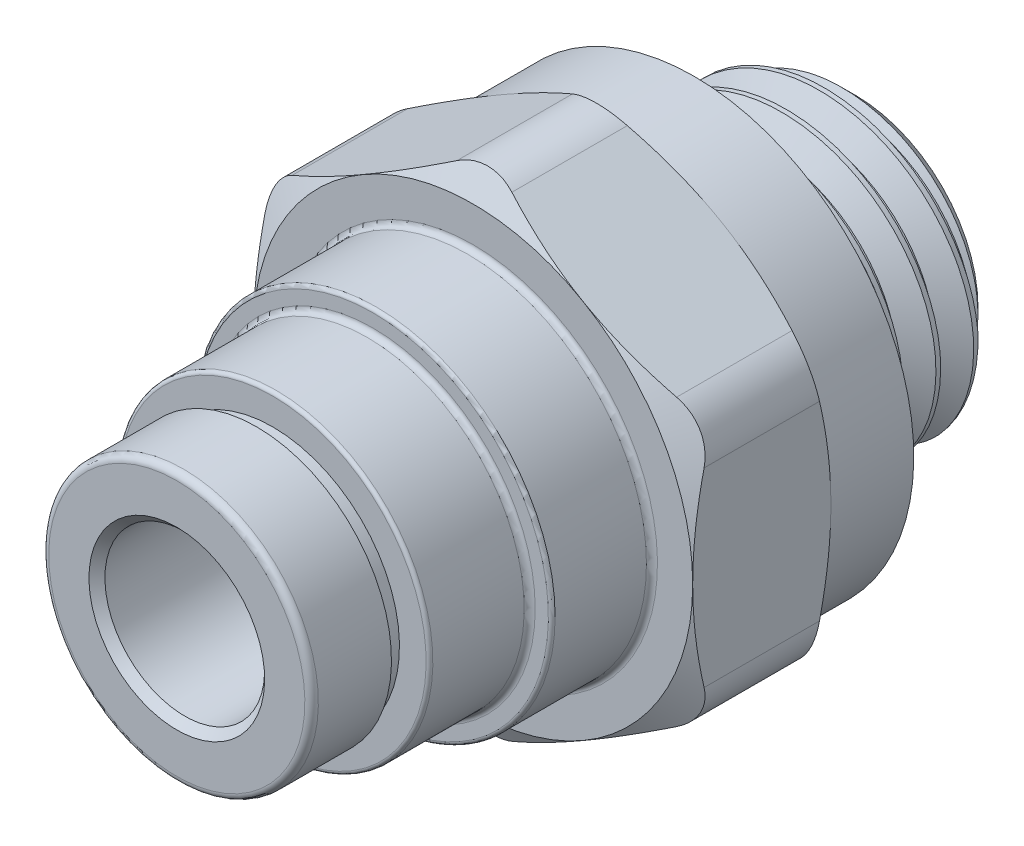
SolidWorks part; units mm, degrees
ref_plane "Front Plane" through (0, 0, 0) normal (0, 0, 1) x (1, 0, 0)
ref_plane "Top Plane" through (0, 0, 0) normal (0, 1, 0) x (1, 0, 0)
ref_plane "Right Plane" through (0, 0, 0) normal (1, 0, 0) x (0, 0, -1)
sketch "Sketch1" plane through (0, 0, 0) normal (1, 0, 0) x (0, 0, -1)
  line L0 (13.4937, 0) -> (-13.4937, 0) construction
  line L1 (-13.4937, -7.112) -> (-13.4938, 7.112) construction
  line L2 (-1.7158, -8.7313) -> (-1.7158, 8.7312) construction
  line L3 (1.4465, -2.3876) -> (1.4465, 2.3876) construction
  line L4 (13.4938, -6) -> (13.4938, 6) construction
  line L6 (13.4938, 6) -> (14.9938, 6) construction
  point P0 (-13.4937, -3.175)
  point P3 (7.0726, 0)
  point P4 (0, 0)
  point P8 (-13.4937, 0)
  point P9 (-13.4937, 3.175)
  point P10 (-13.4937, -5.3594)
  point P11 (-13.4937, 5.3594)
  point P16 (-1.7158, 0)
  point P19 (13.4937, 0)
  point P22 (1.4465, 0)
  dimension "Length" = 26.9875
  dimension "OD2" = 14.224
  dimension "Tube OD" = 6.35
  dimension "OD1" = 10.7188
  dimension "Hex Distance" = 11.778
  dimension "Hex Size" = 17.4625
  dimension "Flow" = 4.7752
  dimension "Insertion" = 14.9403
  dimension "Thread OD" = 12
  dimension "Pitch" = 1.5
  dimension "Hex Length" = 8.7884
sketch "Sketch2" plane through (0, 0, 0) normal (1, 0, 0) x (0, 0, -1)
  line L0 (-13.4938, 3.4925) -> (-13.4938, 5.0914)
  line L1 (-13.2258, 5.3594) -> (-10.3187, 5.3594)
  line L2 (-10.3187, 5.3594) -> (-10.3187, 5.0419)
  line L3 (-10.3187, 5.0419) -> (-9.6837, 5.0419)
  line L4 (-9.6837, 5.0419) -> (-9.6837, 6.1017)
  line L5 (-5.5658, 7.112) -> (-1.9348, 7.112)
  line L6 (-1.7158, -8.7313) -> (-1.7158, 8.7312) construction
  line L7 (-1.7158, 7.3311) -> (-1.7158, 8.7312)
  line L8 (-1.7158, 8.7312) -> (7.0726, 8.7312)
  line L11 (13.4938, 6) -> (13.4938, 2.3876)
  line L12 (13.4938, 2.3876) -> (1.4465, 2.3876)
  line L13 (1.4465, 2.3876) -> (1.4465, 3.175)
  line L14 (1.4465, 3.175) -> (-13.1762, 3.175)
  line L16 (-13.4938, 3.4925) -> (-13.1762, 3.175)
  line L17 (-9.5498, 6.2357) -> (-5.9188, 6.2357)
  line L18 (-5.6998, 6.4548) -> (-5.6998, 6.978)
  line L22 (7.0726, 8.7312) -> (7.0726, 6.7143)
  line L23 (6.7551, 6.1644) -> (7.3901, 6.1644) construction
  line L24 (13.4938, 6) -> (7.4975, 6)
  line L25 (6.7551, 6.1644) -> (7.0726, 6.7143) construction
  line L26 (6.7551, 6.1644) -> (7.3685, 6) construction
  line L27 (7.4975, 6) -> (7.1975, 5.7087)
  arc A0 (-13.2258, 5.3594) -> (-13.4938, 5.0914) centre (-13.2258, 5.0914) ccw
  arc A1 (-1.7158, 7.3311) -> (-1.9348, 7.112) centre (-1.9348, 7.3311) cw
  arc A2 (-5.6998, 6.4548) -> (-5.9188, 6.2357) centre (-5.9188, 6.4548) cw
  circle A4 centre (6.7551, 6.1644) radius 0.635 construction
  arc A5 (7.0726, 6.7143) -> (7.1975, 5.7087) centre (6.7551, 6.1644) cw
  arc A6 (-5.5658, 7.112) -> (-5.6998, 6.978) centre (-5.5658, 6.978) ccw
  arc A7 (-9.5498, 6.2357) -> (-9.6837, 6.1017) centre (-9.5498, 6.1017) ccw
  point P28 (-13.4937, 5.3594)
  point P32 (-1.7158, 7.112)
  point P35 (-5.6998, 6.2357)
  point P40 (-5.6998, 7.112)
  dimension "D6" = 0.268
  dimension "D5" = 0.2191
  dimension "D13" = 0.134
  dimension "D1" = 3.175
  dimension "D2" = 0.635
  dimension "D3" = 0.3175
  dimension "D7" = 0.3175
  dimension "D8" = 45
  dimension "D4" = 0.8763
  dimension "D9" = 60
  dimension "D10" = 0.3175
  dimension "D11" = 15
  dimension "D12" = 0.3
revolve "Revolve1" add sketch "Sketch2" angle 360 about L0
sketch "Sketch3" plane through (0, 0, 1.7158) normal (0, 0, 1) x (1, 0, 0)
  line L0 (0, -7.112) -> (0, 7.112) construction
  line L1 (0, 10.082) -> (-8.7313, 5.041)
  line L2 (-8.7313, 5.041) -> (-8.7312, -5.041)
  line L3 (-8.7312, -5.041) -> (0, -10.082)
  line L4 (0, -10.082) -> (8.7312, -5.041)
  line L5 (8.7312, -5.041) -> (8.7312, 5.041)
  line L6 (8.7312, 5.041) -> (0, 10.082)
  circle A0 centre (0, 0) radius 8.7312 construction
  circle A1 centre (0, 0) radius 8.7312 construction
  circle A2 centre (0, 0) radius 3.175
extrude "Boss-Extrude1" add sketch "Sketch3" against normal blind 5.4927
sketch "Sketch4" plane through (0, 0, 1.7158) normal (0, 0, 1) x (1, 0, 0)
  circle A0 centre (0, 0) radius 8.7312 construction
  circle A1 centre (0, 0) radius 8.7312
extrude "Cut-Extrude1" cut sketch "Sketch4" against normal through all draft 60 flip side to cut
ref_plane "Plane1" through (0, 0, -1.0306) normal (0, 0, 1) x (1, 0, 0)
mirror "Mirror1" about plane through (0, 0, -1.0306) normal (0, 0, 1) of "Cut-Extrude1"
sketch "Sketch9" plane through (0, 0, 0) normal (1, 0, 0) x (0, 0, -1)
  line L0 (1.4465, -3.175) -> (-13.1762, -3.175)
  line L1 (-13.1763, 3.175) -> (1.4465, 3.175)
  line L2 (-13.1763, 3.175) -> (1.4465, 3.175)
  line L3 (1.4465, -3.175) -> (-13.1762, -3.175)
  line L4 (-13.4938, 3.4925) -> (-13.1763, 3.175)
  line L5 (-13.1762, -3.175) -> (-13.4938, -3.4925)
  line L6 (-13.1762, -3.175) -> (-13.4938, -3.4925)
  line L7 (-13.4938, 3.4925) -> (-13.1763, 3.175)
  line L8 (13.4938, -2.3876) -> (1.4465, -2.3876)
  line L9 (1.4465, 2.3876) -> (13.4938, 2.3876)
  line L10 (1.4465, 2.3876) -> (13.4938, 2.3876)
  line L11 (13.4938, -2.3876) -> (1.4465, -2.3876)
  line L12 (1.4465, 3.175) -> (1.4465, 2.3876)
  line L13 (1.4465, -2.3876) -> (1.4465, -3.175)
  line L14 (13.4937, 0) -> (13.4938, -6) construction
  line L16 (13.4938, -6) -> (9.7438, -6) construction
  dimension "D1" = 3.75
fillet "Fillet1" radius 2.1828 6 edges at (8.7312, -5.041, -1.0306) (0, -10.082, -1.0306) (-8.7312, -5.041, -1.0306) (-8.7313, 5.041, -1.0306) (0, 10.082, -1.0306) (8.7312, 5.041, -1.0306)
sketch "Sketch8" plane through (0, 0, 0) normal (1, 0, 0) x (0, 0, -1)
  line L0 (7.3901, -13.0969) -> (7.3901, 13.0969)
  line L1 (0, 0) -> (5.7744, 0) construction
  line L2 (13.4937, 0) -> (-13.4937, 0) construction
  line L4 (7.3901, -6.1644) -> (7.3901, 6.1644) construction
  point P5 (13.4937, 0)
  dimension "D1" = 26.1937
split "Split1" trim tools "Sketch8" bodies to split 113 resulting bodies 109 110
sketch "Sketch6" plane through (0, 0, -13.4938) normal (0, 0, -1) x (-1, 0, 0)
  circle A1 centre (0, 0) radius 6
  circle A5 centre (0, 0) radius 6
  dimension "D1" = 0
curve "Helix/Spiral1" pitch 1.5 height 7.9211 turns 5.2807
sketch "Sketch7" plane through (0, 0, 0) normal (1, 0, 0) x (0, 0, -1)
  line L0 (13.4, 6.1624) -> (14.9, 6.1624) construction
  line L1 (14.9, 6.1624) -> (14.15, 4.8633) construction
  line L2 (14.15, 4.8633) -> (13.4, 6.1624) construction
  line L3 (14.15, 6.1624) -> (14.15, 6) construction
  line L4 (14.15, 6) -> (14.15, 5.0257) construction
  line L5 (14.15, 5.0257) -> (14.15, 4.8633) construction
  line L6 (13.4938, 6) -> (14.8063, 6) construction
  line L7 (14.0563, 5.0257) -> (14.2438, 5.0257)
  line L8 (13.4469, 6.0812) -> (14.8531, 6.0812)
  line L9 (13.4469, 6.0812) -> (14.0563, 5.0257)
  line L10 (14.8531, 6.0812) -> (14.2438, 5.0257)
  point P10 (14.15, 6)
  point P13 (14.15, 5.0257)
  point P16 (14.15, 6.0812)
  dimension "D1" = 1.5
  dimension "D2" = 0.1875
sweep "Cut-Sweep1" cut profiles "Sketch7" path "Helix/Spiral1" align with end faces yes
sketch "Sketch5" plane through (0, 0, -13.4938) normal (0, 0, -1) x (-1, 0, 0)
  circle A0 centre (0, 0) radius 4.8633
extrude "Cut-Extrude2" cut sketch "Sketch5" against normal through all draft 45 flip side to cut
combine bodies "Combine1" operation type add bodies to combine 110 111
equation "\"D6@Sketch2\"=\"OD1@Sketch1\"*0.025"
equation "\"D7@Sketch2\"=\"Tube OD@Sketch1\"*0.05"
equation "\"D1@Fillet1\"=\"Hex Size@Sketch1\"*0.125"
equation "\"D3@Helix/Spiral1\" = \"Length@Sketch1\" - \"Hex Distance@Sketch1\" - \"Hex Length@Sketch1\" + \"Pitch@Sketch1\""
equation "\"D1@Sketch7\"=\"Pitch@Sketch1\""
equation "\"D2@Sketch7\"=\"D1@Sketch7\"/8"
equation "\"D1@Sketch8\"=\"Hex Size@Sketch1\"*1.5"
equation "\"D4@Helix/Spiral1\"=\"Pitch@Sketch1\""
equation "\"D1@Sketch9\"=\"Pitch@Sketch1\"*2.5"
equation "\"D4@Sketch2\"=(\"OD2@Sketch1\"-\"OD1@Sketch1\")/4"
equation "\"D5@Sketch2\"=\"D4@Sketch2\"*0.25"
equation "\"D1@Boss-Extrude1\"=\"Hex Length@Sketch1\"*0.625"
equation "\"D12@Sketch2\"=\"Thread OD@Sketch1\"*0.025"
equation "\"D13@Sketch2\"=\"D6@Sketch2\"*0.5 "
